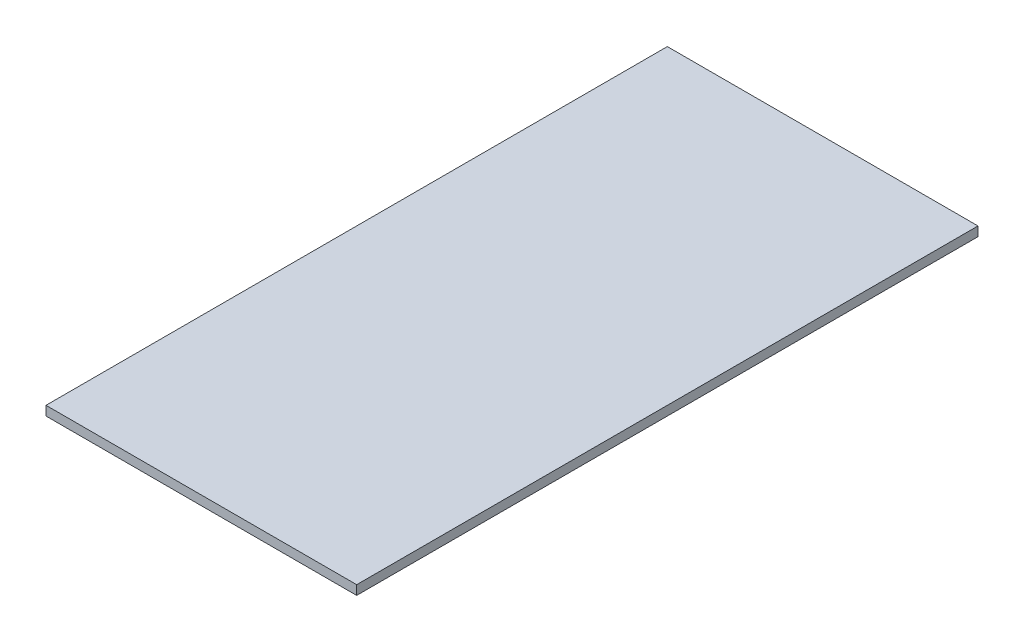
SolidWorks part; units mm, degrees
material "6061 Alloy"
ref_plane "Front Plane" through (0, 0, 0) normal (0, 0, 1) x (1, 0, 0)
ref_plane "Top Plane" through (0, 0, 0) normal (0, 1, 0) x (1, 0, 0)
ref_plane "Right Plane" through (0, 0, 0) normal (1, 0, 0) x (0, 0, -1)
sketch "Sketch1" plane through (0, 0, 0) normal (0, 1, 0) x (1, 0, 0)
  line L1 (-50, -100) -> (50, -100)
  line L2 (-50, -100) -> (-50, 100)
  line L3 (-50, 100) -> (50, 100)
  line L4 (50, -100) -> (50, 100)
  line L5 (-50, -100) -> (50, 100) construction
  line L6 (-50, 100) -> (50, -100) construction
  point P0 (0, 0)
  dimension "D1" = 100
  dimension "D2" = 200
extrude "Boss-Extrude1" add sketch "Sketch1" along normal blind 3
